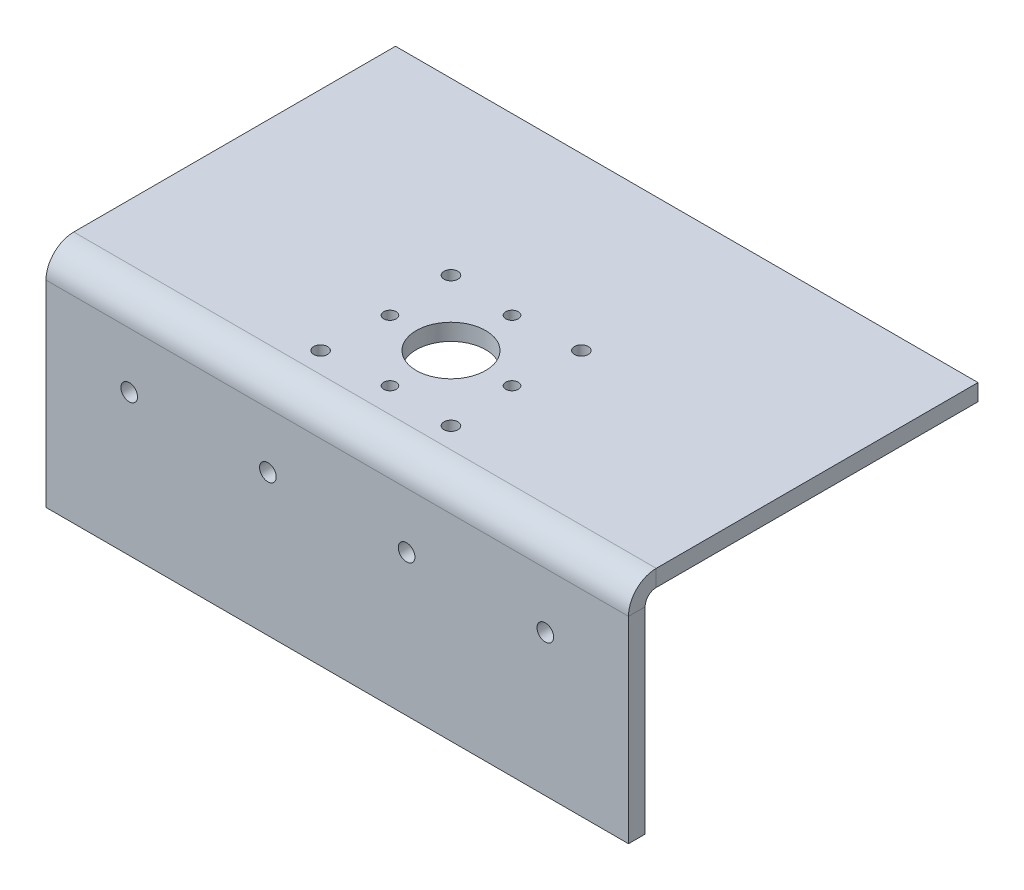
SolidWorks part; units mm, degrees
note: The reader was unsure of these and kept them because the rebuilt part matched: bend radius of "BaseBend1".
ref_plane "Front Plane" through (0, 0, 0) normal (0, 0, 1) x (1, 0, 0)
ref_plane "Top Plane" through (0, 0, 0) normal (0, 1, 0) x (1, 0, 0)
ref_plane "Right Plane" through (0, 0, 0) normal (1, 0, 0) x (0, 0, -1)
sketch "Sketch1" plane through (0, 0, 0) normal (1, 0, 0) x (0, 0, -1)
  line L0 (0, -75) -> (0, 0)
  line L1 (0, 0) -> (120, 0)
  dimension "D1" = 75
  dimension "D2" = 120
base flange "Base-Flange1" sketch "Sketch1" end condition mid plane depth 210 reverse direction no thickness 6 reverse thickness direction yes bend radius 4
bend "BaseBend1" bend radius 4 bend angle 90 parameters "D5"=1
sketch "Sketch6" plane through (0, 6, 0) normal (0, 1, 0) x (1, 0, 0)
  line L0 (0, 35) -> (0, -6) construction
  line L1 (105, -6) -> (-105, -6) construction
  line L3 (-23.5, 11.5) -> (23.5, 11.5) construction
  line L4 (-23.5, 11.5) -> (-23.5, 58.5) construction
  line L5 (-23.5, 58.5) -> (23.5, 58.5) construction
  line L6 (23.5, 11.5) -> (23.5, 58.5) construction
  line L7 (-23.5, 11.5) -> (23.5, 58.5) construction
  line L8 (-23.5, 58.5) -> (23.5, 11.5) construction
  circle A0 centre (0, 35) radius 12.5
  circle A1 centre (23.5, 58.5) radius 2.5
  circle A2 centre (-23.5, 58.5) radius 2.5
  circle A3 centre (-23.5, 11.5) radius 2.5
  circle A4 centre (23.5, 11.5) radius 2.5
  dimension "D1" = 25
  dimension "D4" = 5
  dimension "D2" = 41
  dimension "D3" = 47
extrude "Cut-Extrude1" cut sketch "Sketch6" against normal blind 10
sketch "Sketch7" plane through (0, 0, 6) normal (0, 0, 1) x (1, 0, 0)
  line L0 (-75, -24) -> (75, -24) construction
  line L1 (0, -24) -> (0, 6) construction
  line L2 (105, 6) -> (-105, 6) construction
  circle A0 centre (-75, -24) radius 3
  circle A1 centre (-25, -24) radius 3
  circle A2 centre (25, -24) radius 3
  circle A3 centre (75, -24) radius 3
  dimension "D5" = 6
  dimension "D1" = 150
  dimension "D2" = 50
  dimension "D3" = 50
  dimension "D4" = 30
extrude "Cut-Extrude2" cut sketch "Sketch7" against normal blind 10
sketch "Sketch8" plane through (0, 6, 0) normal (0, 1, 0) x (1, 0, 0)
  line L0 (0, 35) -> (0, 13) construction
  circle A0 centre (0, 35) radius 22 construction
  circle A1 centre (0, 13) radius 2.25
  circle A2 centre (-22, 35) radius 2.25
  circle A3 centre (0, 57) radius 2.25
  circle A4 centre (22, 35) radius 2.25
  point P5 (0, 0)
  point P6 (0, 0)
  point P14 (0, 35)
  dimension "D1" = 44
  dimension "D2" = 4.5
  dimension "D3" = 4
extrude "Cut-Extrude3" cut sketch "Sketch8" against normal blind 10
sketch "Bend-Lines1" [suppressed] plane through (0, 0, 0) normal (0, 1, 0) x (1, 0, 0)
sketch "Bounding-Box1" [suppressed] plane through (0, 0, 0) normal (0, 1, 0) x (1, 0, 0)
sheet metal parameters "Sheet-Metal1" thickness 6 parameters "D1"=4
flat pattern "Flat-Pattern1" [suppressed]
sketch "Bend-Lines2" plane through (0, 6, 0) normal (0, 1, 0) x (1, 0, 0)
  line L0 (105, -1.4978) -> (-105, -1.4978) construction
  line L1 (105, -1.4978) -> (-105, -1.4978) construction
sketch3d "Bounding-Box2" [suppressed]
  line L0 (0, -77.9956, 0) -> (-210, -77.9956, 0) construction
  line L1 (0, 120, 0) -> (-210, 120, 0) construction
  line L2 (0, -77.9956, 0) -> (0, 120, 0) construction
  line L3 (-210, -77.9956, 0) -> (-210, 120, 0) construction
bend of the flat pattern "Flatten-<BaseBend1>1"
sheet metal parameters "Sheet-Metal2" thickness 6 parameters "D1"=4
flat pattern "Flat-Pattern1"
sketch "Bend-Lines2" plane through (0, 6, 0) normal (0, 1, 0) x (1, 0, 0)
  line L0 (105, -1.4978) -> (-105, -1.4978) construction
  line L1 (105, -1.4978) -> (-105, -1.4978) construction
sketch3d "Bounding-Box2" [suppressed]
  line L0 (0, -77.9956, 0) -> (-210, -77.9956, 0) construction
  line L1 (0, 120, 0) -> (-210, 120, 0) construction
  line L2 (0, -77.9956, 0) -> (0, 120, 0) construction
  line L3 (-210, -77.9956, 0) -> (-210, 120, 0) construction
bend of the flat pattern "Flatten-<BaseBend1>1"
sheet metal parameters "Sheet-Metal3" thickness 6 parameters "D1"=4
flat pattern "Flat-Pattern1"
sketch "Bend-Lines2" plane through (0, 6, 0) normal (0, 1, 0) x (1, 0, 0)
  line L0 (105, -1.4978) -> (-105, -1.4978) construction
  line L1 (105, -1.4978) -> (-105, -1.4978) construction
sketch3d "Bounding-Box2" [suppressed]
  line L0 (0, -77.9956, 0) -> (-210, -77.9956, 0) construction
  line L1 (0, 120, 0) -> (-210, 120, 0) construction
  line L2 (0, -77.9956, 0) -> (0, 120, 0) construction
  line L3 (-210, -77.9956, 0) -> (-210, 120, 0) construction
bend of the flat pattern "Flatten-<BaseBend1>1"
sheet metal parameters "Sheet-Metal4" thickness 6 parameters "D1"=4
flat pattern "Flat-Pattern1"
sketch "Bend-Lines2" plane through (0, 6, 0) normal (0, 1, 0) x (1, 0, 0)
  line L0 (105, -1.4978) -> (-105, -1.4978) construction
  line L1 (105, -1.4978) -> (-105, -1.4978) construction
sketch3d "Bounding-Box2" [suppressed]
  line L0 (0, -77.9956, 0) -> (-210, -77.9956, 0) construction
  line L1 (0, 120, 0) -> (-210, 120, 0) construction
  line L2 (0, -77.9956, 0) -> (0, 120, 0) construction
  line L3 (-210, -77.9956, 0) -> (-210, 120, 0) construction
bend of the flat pattern "Flatten-<BaseBend1>1"
